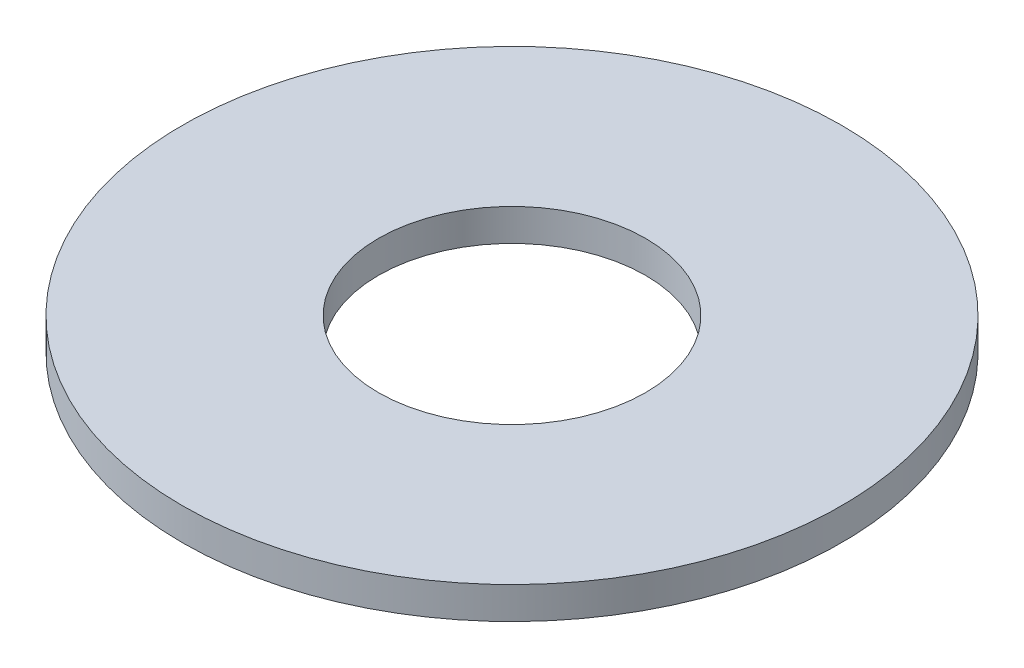
SolidWorks part; units mm, degrees
ref_plane "Front Plane" through (0, 0, 0) normal (0, 0, 1) x (1, 0, 0)
ref_plane "Top Plane" through (0, 0, 0) normal (0, 1, 0) x (1, 0, 0)
ref_plane "Right Plane" through (0, 0, 0) normal (1, 0, 0) x (0, 0, -1)
sketch "Sketch1" plane through (0, 0, 0) normal (0, 1, 0) x (1, 0, 0)
  circle A0 centre (0, 0) radius 92.5
  dimension "FLANGE_OD" = 185
extrude "Boss-Extrude1" add sketch "Sketch1" along normal blind 9
sketch "Sketch2" plane through (0, 0, 0) normal (0, 1, 0) x (1, 0, 0)
  circle A0 centre (0, 0) radius 37.5
  dimension "BORE_D" = 75
extrude "Cut-Extrude1" cut sketch "Sketch2" along normal through all
sketch "Sketch3" plane through (0, 9, 0) normal (0, 1, 0) x (1, 0, 0)
  circle A0 centre (0, 0) radius 27.0593 construction
  circle A1 centre (-27.0593, 0) radius 6.2867
  dimension "BOLT_D" = 12.5734
  dimension "BOLT_PCD" = 54.1187
extrude "Cut-Extrude2" cut sketch "Sketch3" against normal blind 7.3341 rebuild error yes
pattern_circular "CirPattern1" count 4 over 360 rebuild error yes
